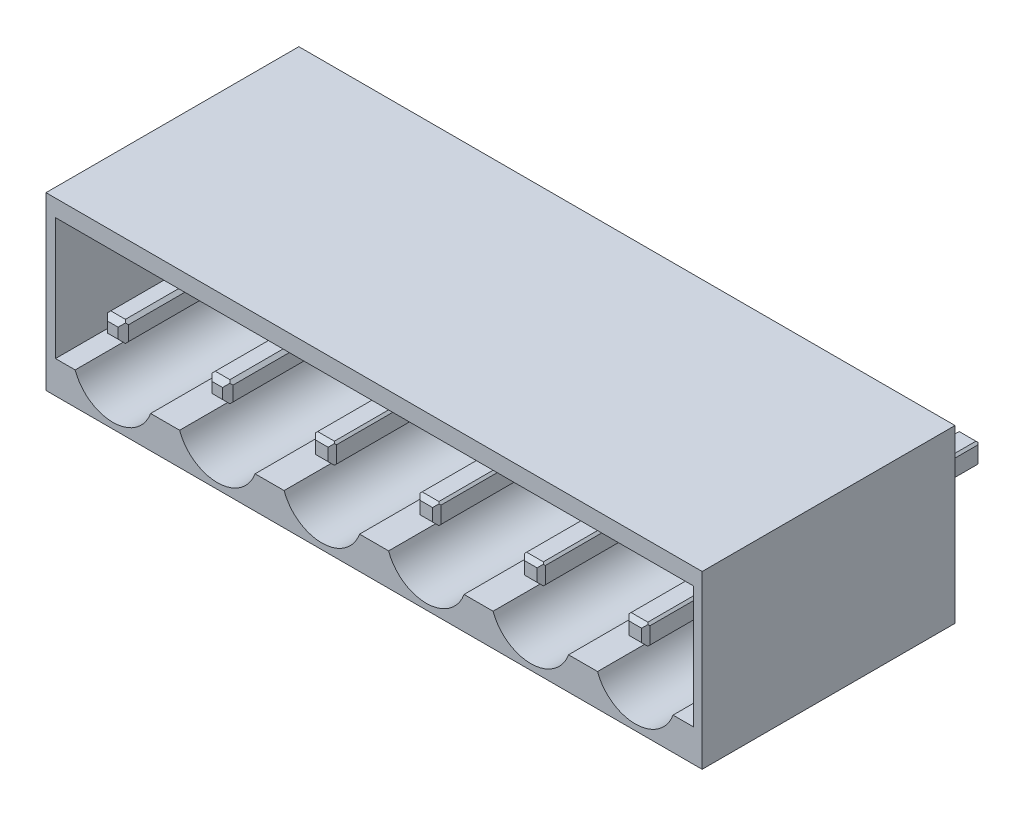
SolidWorks part; units mm, degrees
ref_plane "Спереди" through (0, 0, 0) normal (0, 0, 1) x (1, 0, 0)
ref_plane "Сверху" through (0, 0, 0) normal (0, 1, 0) x (1, 0, 0)
ref_plane "Справа" through (0, 0, 0) normal (1, 0, 0) x (0, 0, -1)
sketch "Эскиз1" plane through (0, 0, 0) normal (0, 0, 1) x (1, 0, 0)
  line L1 (-15.7, 4.1) -> (15.7, 4.1)
  line L2 (-15.7, 4.1) -> (-15.7, -4.1)
  line L3 (-15.7, -4.1) -> (15.7, -4.1)
  line L4 (15.7, 4.1) -> (15.7, -4.1)
  line L5 (-15.7, 4.1) -> (15.7, -4.1) construction
  line L6 (-15.7, -4.1) -> (15.7, 4.1) construction
  point P0 (0, 0)
  dimension "D1" = 8.2
  dimension "D2" = 31.4
extrude "Бобышка-Вытянуть1" add sketch "Эскиз1" along normal blind 12.1
sketch "Эскиз4" plane through (0, 0, 12.1) normal (0, 0, 1) x (1, 0, 0)
  circle A0 centre (-12.5, 0) radius 1.25
  circle A1 centre (-7.5, 0) radius 1.25
  circle A2 centre (-2.5, 0) radius 1.25
  circle A3 centre (2.5, 0) radius 1.25
  circle A4 centre (7.5, 0) radius 1.25
  circle A5 centre (12.5, 0) radius 1.25
  dimension "D1" = 2.5
  dimension "D2" = 3.2
  dimension "D5" = 2
  dimension "D3" = 2
  dimension "D4" = 2
  dimension "D6" = 3
extrude "Вырез-Вытянуть3" cut sketch "Эскиз4" against normal blind 8
sketch "Эскиз5" plane through (0, 0, 12.1) normal (0, 0, 1) x (1, 0, 0)
  line L0 (-15.2456, 0) -> (-15.2456, 3.2929)
  line L1 (-15.2456, 3.2929) -> (-4.7215, 3.2929)
  line L4 (-15.2456, -2.549) -> (-15.2456, 0)
  line L5 (-5.6942, -2.549) -> (-4.3058, -2.549)
  line L6 (-14.3058, -2.549) -> (-15.2456, -2.549)
  line L7 (-10.6942, -2.549) -> (-9.3058, -2.549)
  line L11 (-4.7215, 3.2929) -> (0.2785, 3.2929)
  line L13 (-5.6942, -2.549) -> (-4.3058, -2.549) [skipped]
  line L15 (-0.6942, -2.549) -> (0.6942, -2.549)
  line L16 (0.2785, 3.2929) -> (5.2785, 3.2929)
  line L17 (9.3058, -2.549) -> (10.6942, -2.549)
  line L18 (14.3058, -2.549) -> (15.2785, -2.549)
  line L19 (15.2785, 3.2929) -> (15.2785, -2.549)
  line L20 (4.3058, -2.549) -> (5.6942, -2.549)
  line L21 (5.2785, 3.2929) -> (15.2785, 3.2929)
  arc A1 (-4.3058, -2.549) -> (-0.6942, -2.549) centre (-2.5, -1.9) ccw
  arc A2 (0.6942, -2.549) -> (4.3058, -2.549) centre (2.5, -1.9) ccw
  arc A4 (5.6942, -2.549) -> (9.3058, -2.549) centre (7.5, -1.9) ccw
  arc A5 (-14.3058, -2.549) -> (-10.6942, -2.549) centre (-12.5, -1.9) ccw
  arc A6 (-9.3058, -2.549) -> (-5.6942, -2.549) centre (-7.5, -1.9) ccw
  arc A7 (10.6942, -2.549) -> (14.3058, -2.549) centre (12.5, -1.9) ccw
  dimension "D1" = 3.2
  dimension "D2" = 2.2
  dimension "D3" = 2
  dimension "D4" = 2
  dimension "D5" = 2
  dimension "D6" = 2
extrude "Вырез-Вытянуть4" cut sketch "Эскиз5" against normal blind 7.8
sketch "Эскиз7" plane through (0, 0, 4.1) normal (0, 0, 1) x (1, 0, 0)
  line L0 (-8, 0.5) -> (-7, 0.5)
  line L1 (-13, 0.5) -> (-12, 0.5)
  line L2 (-13, 0.5) -> (-13, -0.5)
  line L3 (-13, -0.5) -> (-12, -0.5)
  line L4 (-12, 0.5) -> (-12, -0.5)
  line L5 (-13, 0.5) -> (-12, -0.5) construction
  line L6 (-13, -0.5) -> (-12, 0.5) construction
  line L7 (-8, 0.5) -> (-8, -0.5)
  line L8 (-8, -0.5) -> (-7, -0.5)
  line L9 (-7, 0.5) -> (-7, -0.5)
  line L10 (-8, 0.5) -> (-7, -0.5) construction
  line L11 (-8, -0.5) -> (-7, 0.5) construction
  line L12 (-3, 0.5) -> (-2, 0.5)
  line L13 (-3, 0.5) -> (-3, -0.5)
  line L14 (-3, -0.5) -> (-2, -0.5)
  line L15 (-2, 0.5) -> (-2, -0.5)
  line L16 (-3, 0.5) -> (-2, -0.5) construction
  line L17 (-3, -0.5) -> (-2, 0.5) construction
  line L18 (2, 0.5) -> (3, 0.5)
  line L19 (2, 0.5) -> (2, -0.5)
  line L20 (2, -0.5) -> (3, -0.5)
  line L21 (3, 0.5) -> (3, -0.5)
  line L22 (2, 0.5) -> (3, -0.5) construction
  line L23 (2, -0.5) -> (3, 0.5) construction
  line L24 (7, 0.5) -> (8, 0.5)
  line L25 (7, 0.5) -> (7, -0.5)
  line L26 (7, -0.5) -> (8, -0.5)
  line L27 (8, 0.5) -> (8, -0.5)
  line L28 (12, 0.5) -> (13, 0.5)
  line L29 (12, 0.5) -> (12, -0.5)
  line L30 (12, -0.5) -> (13, -0.5)
  line L31 (13, 0.5) -> (13, -0.5)
  line L32 (7, 0.5) -> (8, -0.5) construction
  line L33 (7, -0.5) -> (8, 0.5) construction
  line L34 (12, 0.5) -> (13, -0.5) construction
  line L35 (12, -0.5) -> (13, 0.5) construction
  point P0 (-12.5, 0)
  point P7 (-7.5, 0)
  point P12 (-2.5, 0)
  point P17 (2.5, 0)
  point P23 (7.5, 0)
  point P28 (12.5, 0)
  dimension "D1" = 1
  dimension "D2" = 1
  dimension "D3" = 2
  dimension "D4" = 2
  dimension "D5" = 2
  dimension "D6" = 2
extrude "Бобышка-Вытянуть2" add sketch "Эскиз7" along normal blind 8
chamfer "Фаска1" distance 0.15 angle 45 8 edges at (-8, -0.5, 8.1) (-8, 0.5, 8.1) (-7, 0.5, 8.1) (-7, -0.5, 8.1) (-12, -0.5, 8.1) (-12, 0.5, 8.1) (-13, -0.5, 8.1) (-13, 0.5, 8.1)
chamfer "Фаска2" distance 0.25 angle 45 8 edges at (-8, 0, 12.1) (-7.5, 0.5, 12.1) (-7, 0, 12.1) (-7.5, -0.5, 12.1) (-12, 0, 12.1) (-12.5, -0.5, 12.1) (-13, 0, 12.1) (-12.5, 0.5, 12.1)
sketch "Эскиз8" plane through (0, -4.1, 0) normal (0, 0, 1) x (-1, 0, 0)
  line L0 (8, -4.25) -> (7, -4.25)
  line L1 (13, -4.25) -> (12, -4.25)
  line L2 (13, -4.25) -> (13, -3.25)
  line L3 (13, -3.25) -> (12, -3.25)
  line L4 (12, -4.25) -> (12, -3.25)
  line L5 (13, -4.25) -> (12, -3.25) construction
  line L6 (13, -3.25) -> (12, -4.25) construction
  line L7 (8, -4.25) -> (8, -3.25)
  line L8 (8, -3.25) -> (7, -3.25)
  line L9 (7, -4.25) -> (7, -3.25)
  line L10 (8, -4.25) -> (7, -3.25) construction
  line L11 (8, -3.25) -> (7, -4.25) construction
  line L12 (3, -4.25) -> (2, -4.25)
  line L13 (3, -4.25) -> (3, -3.25)
  line L14 (3, -3.25) -> (2, -3.25)
  line L15 (2, -4.25) -> (2, -3.25)
  line L16 (3, -4.25) -> (2, -3.25) construction
  line L17 (3, -3.25) -> (2, -4.25) construction
  line L18 (-2, -4.25) -> (-3, -4.25)
  line L19 (-2, -4.25) -> (-2, -3.25)
  line L20 (-2, -3.25) -> (-3, -3.25)
  line L21 (-3, -4.25) -> (-3, -3.25)
  line L22 (-2, -4.25) -> (-3, -3.25) construction
  line L23 (-2, -3.25) -> (-3, -4.25) construction
  line L24 (-7, -4.25) -> (-8, -4.25)
  line L25 (-7, -4.25) -> (-7, -3.25)
  line L26 (-7, -3.25) -> (-8, -3.25)
  line L27 (-8, -4.25) -> (-8, -3.25)
  line L28 (-12, -4.25) -> (-13, -4.25)
  line L29 (-12, -4.25) -> (-12, -3.25)
  line L30 (-12, -3.25) -> (-13, -3.25)
  line L31 (-13, -4.25) -> (-13, -3.25)
  line L32 (-7, -4.25) -> (-8, -3.25) construction
  line L33 (-7, -3.25) -> (-8, -4.25) construction
  line L34 (-12, -4.25) -> (-13, -3.25) construction
  line L35 (-12, -3.25) -> (-13, -4.25) construction
  point P0 (12.5, -3.75)
  point P7 (7.5, -3.75)
  point P12 (2.5, -3.75)
  point P18 (-2.5, -3.75)
  point P23 (-7.5, -3.75)
  point P28 (-12.5, -3.75)
  dimension "D1" = 1
  dimension "D2" = 1
  dimension "D3" = 3.2
  dimension "D4" = 4.45
  dimension "D5" = 2
  dimension "D6" = 2
  dimension "D7" = 2
  dimension "D8" = 2
extrude "Бобышка-Вытянуть3" add sketch "Эскиз8" against normal blind 4
chamfer "Фаска6" distance 0.1 angle 45 4 edges at (-3, -0.5, 8.1) (-2, -0.5, 8.1) (-2, 0.5, 8.1) (-3, 0.5, 8.1)
chamfer "Фаска7" distance 0.2 angle 45 4 edges at (-2, 0, 12.1) (-2.5, -0.5, 12.1) (-3, 0, 12.1) (-2.5, 0.5, 12.1)
chamfer "Фаска10" distance 0.1 angle 45 12 edges at (-13, -0.85, -2) (-13, 0.15, -2) (-8, -0.85, -2) (-8, 0.15, -2) (-3, -0.85, -2) (-3, 0.15, -2) (-12, -0.85, -2) (-7, -0.85, -2) (-2, -0.85, -2) (-12, 0.15, -2) (-7, 0.15, -2) (-2, 0.15, -2)
chamfer "Фаска11" distance 0.2 angle 45 12 edges at (-12, -0.35, -4) (-12.5, 0.15, -4) (-13, -0.35, -4) (-12.5, -0.85, -4) (-7.5, -0.85, -4) (-8, -0.35, -4) (-7.5, 0.15, -4) (-7, -0.35, -4) (-3, -0.35, -4) (-2.5, 0.15, -4) (-2, -0.35, -4) (-2.5, -0.85, -4)
chamfer "Фаска12" distance 0.1 angle 45 20 edges at (2, 0.15, -2) (2, -0.85, -2) (3, 0.15, -2) (3, -0.85, -2) (12, -0.5, 8.1) (7, -0.5, 8.1) (7, 0.5, 8.1) (8, 0.5, 8.1) (8, -0.5, 8.1) (13, -0.5, 8.1) (12, 0.5, 8.1) (13, 0.5, 8.1) (12, -0.85, -2) (12, 0.15, -2) (13, -0.85, -2) (13, 0.15, -2) (8, -0.85, -2) (8, 0.15, -2) (7, -0.85, -2) (7, 0.15, -2)
chamfer "Фаска13" distance 0.2 angle 45 4 edges at (2.5, 0.15, -4) (3, -0.35, -4) (2, -0.35, -4) (2.5, -0.85, -4)
chamfer "Фаска14" distance 0.1 angle 45 4 edges at (3, 0.5, 8.1) (3, -0.5, 8.1) (2, -0.5, 8.1) (2, 0.5, 8.1)
chamfer "Фаска15" distance 0.2 angle 45 20 edges at (2, 0, 12.1) (2.5, -0.5, 12.1) (3, 0, 12.1) (2.5, 0.5, 12.1) (7, -0.35, -4) (7.5, -0.85, -4) (8, -0.35, -4) (7.5, 0.15, -4) (12, -0.35, -4) (12.5, -0.85, -4) (13, -0.35, -4) (12.5, 0.15, -4) (13, 0, 12.1) (12.5, -0.5, 12.1) (12, 0, 12.1) (12.5, 0.5, 12.1) (7.5, -0.5, 12.1) (8, 0, 12.1) (7, 0, 12.1) (7.5, 0.5, 12.1)
